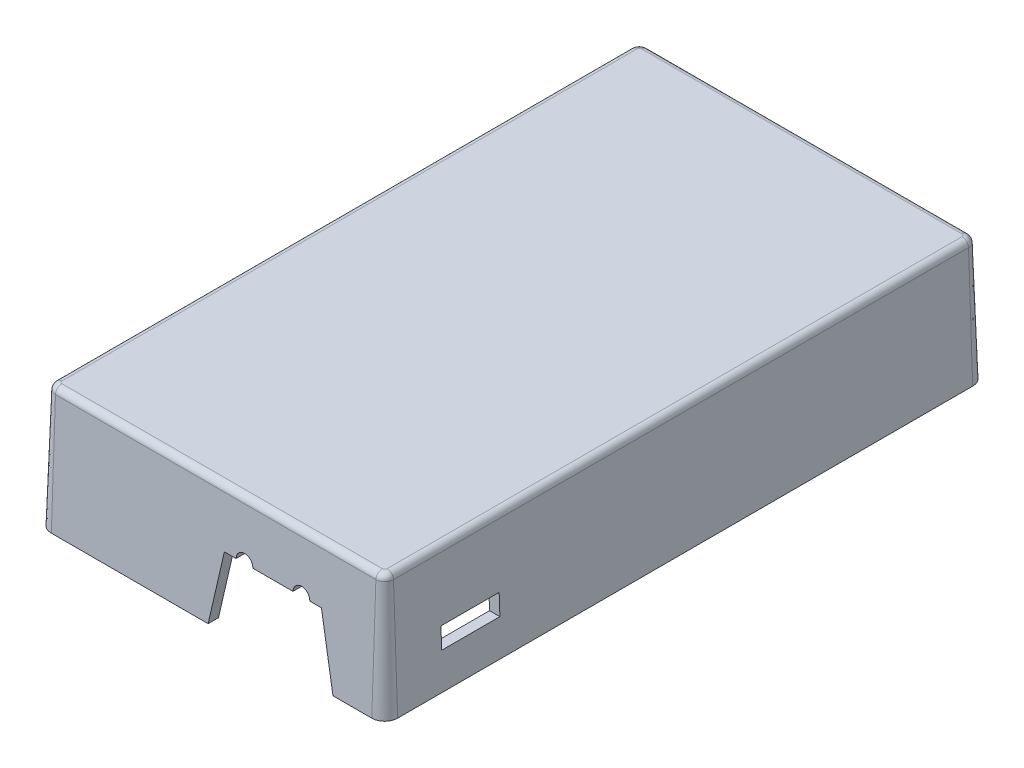
SolidWorks part; units mm, degrees
ref_plane "Спереди" through (0, 0, 0) normal (0, 0, 1) x (1, 0, 0)
ref_plane "Сверху" through (0, 0, 0) normal (0, 1, 0) x (1, 0, 0)
ref_plane "Справа" through (0, 0, 0) normal (1, 0, 0) x (0, 0, -1)
sketch "Sketch1" plane through (0, 0, 0) normal (0, 1, 0) x (1, 0, 0)
  line L0 (12.385, -23.225) -> (-12.385, -23.225)
  line L1 (13.385, -22.225) -> (13.385, 22.225)
  line L2 (12.385, 23.225) -> (-12.385, 23.225)
  line L3 (-13.385, -22.225) -> (-13.385, 22.225)
  arc A0 (13.385, 22.225) -> (12.385, 23.225) centre (12.385, 22.225) ccw
  arc A1 (12.385, -23.225) -> (13.385, -22.225) centre (12.385, -22.225) ccw
  arc A2 (-13.385, -22.225) -> (-12.385, -23.225) centre (-12.385, -22.225) ccw
  arc A3 (-13.385, 22.225) -> (-12.385, 23.225) centre (-12.385, 22.225) cw
  dimension "D1" = 1
  dimension "D2" = 46.45
  dimension "D3" = 26.77
extrude "Boss-Extrude1" add sketch "Sketch1" along normal blind 9.6 draft 2
shell "Shell1" thickness 0.8 removed face at (0, 0, 0)
fillet "Fillet1" radius 0.5 8 edges at (13.0498, 9.6, 0) (12.8551, 9.6, 22.6951) (0, 9.6, 22.8898) (-12.8551, 9.6, 22.6951) (-13.0498, 9.6, 0) (-12.8551, 9.6, -22.6951) (0, 9.6, -22.8898) (12.8551, 9.6, -22.6951)
sketch "Sketch2" plane through (0, 0, 0) normal (0, 0, 1) x (1, 0, 0)
  line L0 (9.385, 0) -> (8.31, 5.2591)
  line L1 (-12.385, 0) -> (12.385, 0) construction
  line L2 (8.31, 5.2591) -> (7.41, 5.2591)
  line L3 (0.81, 5.2591) -> (-0.265, 0)
  line L4 (-0.265, 0) -> (9.385, 0)
  line L5 (4.56, 5.2591) -> (4.56, 1.8087) construction
  line L6 (1.71, 5.2591) -> (0.81, 5.2591)
  line L7 (6.11, 5.2591) -> (3.01, 5.2591)
  line L8 (12.385, 9.1174) -> (12.385, 0) construction
  arc A0 (3.01, 5.2591) -> (1.71, 5.2591) centre (2.36, 5.2591) ccw
  arc A1 (6.11, 5.2591) -> (7.41, 5.2591) centre (6.76, 5.2591) cw
  dimension "D4" = 1.3
  dimension "D1" = 7.5
  dimension "D2" = 9.65
  dimension "D3" = 4.825
  dimension "D5" = 2.2
  dimension "D6" = 3
extrude "Cut-Extrude1" cut sketch "Sketch2" against normal up to surface (0.9841 mm away) from vertex up to face at (0, 4.8378, 22.2556) starting at point (12.385, 0, 23.225)
sketch "Sketch3" plane through (0, 0, 0) normal (0, 0, 1) x (1, 0, 0)
  line L0 (12.385, 0) -> (-12.385, 0) construction
  line L1 (10.67, 0) -> (-10.67, 0)
  line L2 (10.67, 0) -> (10.67, 5.93)
  line L3 (10.67, 5.93) -> (-10.67, 5.93)
  line L4 (-10.67, 0) -> (-10.67, 5.93)
  line L5 (0, 8.8) -> (0, 0) construction
  line L6 (10.67, 6.38) -> (2.27, 6.38)
  line L7 (10.67, 6.38) -> (10.67, 8.8)
  line L8 (10.67, 8.8) -> (2.27, 8.8)
  line L9 (2.27, 7.38) -> (2.27, 8.8)
  line L10 (-10.67, 6.38) -> (-2.27, 6.38)
  line L11 (-10.67, 6.38) -> (-10.67, 8.8)
  line L12 (-10.67, 8.8) -> (-2.27, 8.8)
  line L13 (-2.27, 6.38) -> (-2.27, 7.8)
  line L14 (12.2772, 8.8) -> (-12.2772, 8.8) construction
  line L16 (2.27, 6.38) -> (1.57, 6.38)
  line L18 (2.27, 7.38) -> (1.57, 7.38)
  line L19 (1.57, 6.38) -> (1.57, 7.38)
  line L20 (-2.27, 8.8) -> (-1.57, 8.8)
  line L22 (-2.27, 7.8) -> (-1.57, 7.8)
  line L23 (-1.57, 8.8) -> (-1.57, 7.8)
  dimension "D1" = 21.34
  dimension "D2" = 10.67
  dimension "D3" = 5.93
  dimension "D4" = 0.45
  dimension "D5" = 8.4
  dimension "D6" = 8.4
  dimension "D7" = 9.1
  dimension "D8" = 9.1
  dimension "D9" = 1
  dimension "D10" = 1
extrude "Cut-Extrude2" cut sketch "Sketch3" along normal up to surface (0.8005 mm away) from vertex up to face at (0, 4.8378, -22.2556) starting at point (-12.385, 0, -23.225)
sketch "Sketch4" plane through (0, 0, 0) normal (1, 0, 0) x (0, 0, -1)
  line L0 (22.225, 0) -> (-22.225, 0) construction
  line L1 (-14.225, 4.35) -> (-18.725, 4.35)
  line L2 (-14.225, 4.35) -> (-14.225, 2.75)
  line L3 (-14.225, 2.75) -> (-18.725, 2.75)
  line L4 (-18.725, 4.35) -> (-18.725, 2.75)
  dimension "D1" = 4.5
  dimension "D2" = 1.6
  dimension "D3" = 2.75
  dimension "D4" = 4.5
extrude "Cut-Extrude3" cut sketch "Sketch4" against normal through all both and the other way through all
